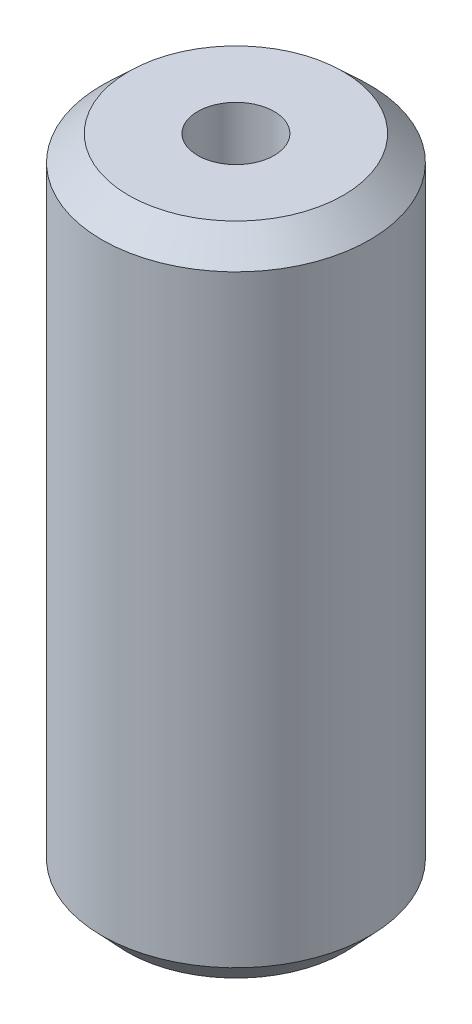
SolidWorks part; units mm, degrees
ref_plane "Front Plane" through (0, 0, 0) normal (0, 0, 1) x (1, 0, 0)
ref_plane "Top Plane" through (0, 0, 0) normal (0, 1, 0) x (1, 0, 0)
ref_plane "Right Plane" through (0, 0, 0) normal (1, 0, 0) x (0, 0, -1)
sketch "Sketch1" plane through (0, 0, 0) normal (0, 1, 0) x (1, 0, 0)
  circle A0 centre (0, 0) radius 22.5
  dimension "SHAFT_OD" = 45
extrude "Boss-Extrude1" add sketch "Sketch1" along normal blind 109.9284
sketch "Sketch2" plane through (0, 0, 0) normal (0, 1, 0) x (1, 0, 0)
  circle A0 centre (0, 0) radius 6.4138
  dimension "BORE_D" = 12.8275
extrude "Cut-Extrude1" cut sketch "Sketch2" along normal through all
chamfer "Chamfer1" distance 4.2228 angle 46.709 2 edges at (0, 109.9284, 22.5) (0, 0, 22.5) first distance on face at (0, 109.9284, 22.5) first distance on face at (0, 0, 6.4138)
